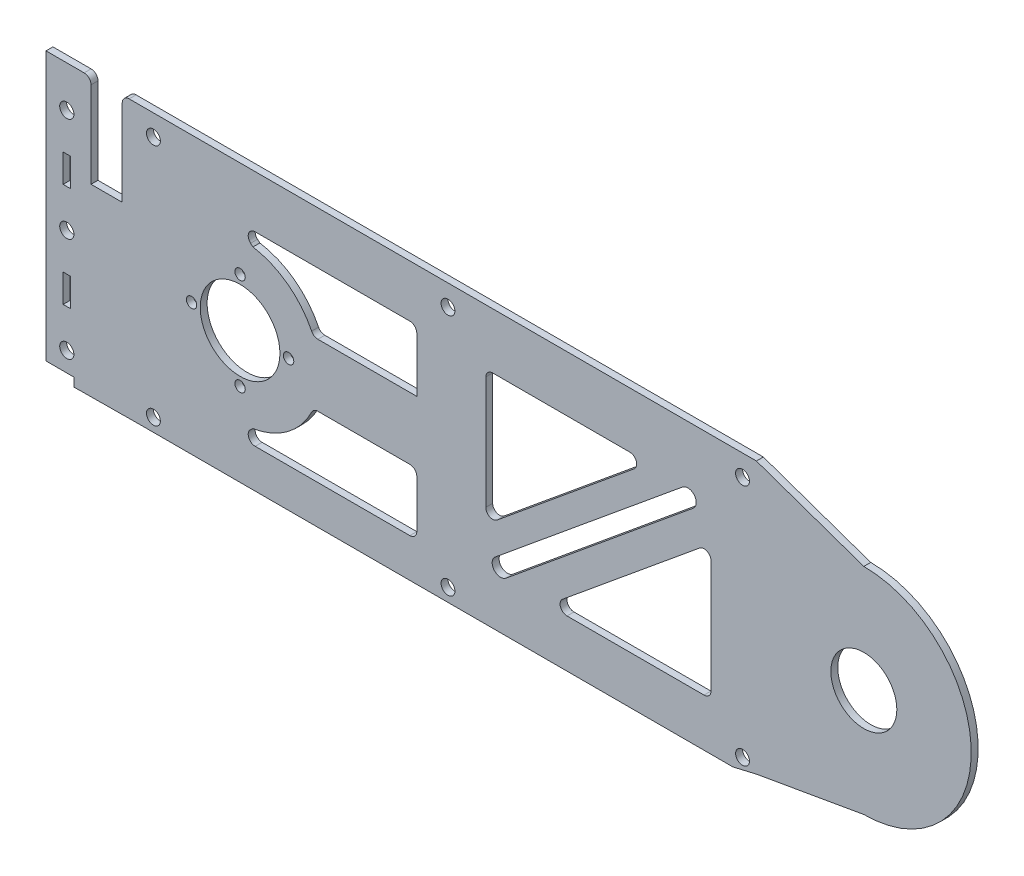
SolidWorks part; units mm, degrees
ref_plane "前视基准面" through (0, 0, 0) normal (0, 0, 1) x (1, 0, 0)
ref_plane "上视基准面" through (0, 0, 0) normal (0, 1, 0) x (1, 0, 0)
ref_plane "右视基准面" through (0, 0, 0) normal (1, 0, 0) x (0, 0, -1)
sketch "草图1" plane through (0, 0, 0) normal (0, 0, 1) x (1, 0, 0)
  line L0 (1.6429, 32.0043) -> (1.6429, 27.9043)
  line L1 (1.6429, 18.9543) -> (1.6429, 10.9543) construction
  line L2 (0.5929, 10.9043) -> (2.6929, 10.9043)
  line L3 (0.5929, 10.9043) -> (0.5929, 19.0043)
  line L4 (0.5929, 19.0043) -> (2.6929, 19.0043)
  line L5 (2.6929, 10.9043) -> (2.6929, 19.0043)
  line L6 (0.5929, 10.9043) -> (2.6929, 19.0043) construction
  line L7 (0.5929, 19.0043) -> (2.6929, 10.9043) construction
  line L12 (1.6429, -0.0457) -> (-4.3571, -0.0457) construction
  line L13 (-4.3571, -0.0457) -> (-4.3571, 41.8043)
  line L14 (-4.3571, 41.8043) -> (262.6429, 41.8043) construction
  line L15 (262.6429, 41.8043) -> (262.6429, -38.1957) construction
  line L18 (51.6429, -0.0457) -> (97.8433, -0.0457) construction
  line L19 (51.6429, -0.0457) -> (231.6429, -0.0457) construction
  line L21 (200.6429, -0.0457) -> (200.6429, 41.8043) construction
  line L23 (200.6429, 41.8043) -> (231.6429, 30.9543)
  line L26 (231.6429, -31.0457) -> (200.6561, -36.4559)
  line L28 (-4.3571, 41.8043) -> (8.6429, 41.8043)
  line L29 (1.6429, -0.0457) -> (37.6429, -0.0457) construction
  line L32 (22.4658, -38.0457) -> (193.8469, -38.0457)
  line L42 (17.6429, 14.9543) -> (17.6429, 41.8043)
  line L43 (17.6429, 41.8043) -> (200.6429, 41.8043)
  line L44 (8.6429, 41.8043) -> (8.6429, 14.9543)
  line L45 (8.6429, 14.9543) -> (17.6429, 14.9543)
  line L47 (193.8469, -38.0457) -> (200.6561, -36.4559)
  line L48 (0.5929, -19.0957) -> (2.6929, -10.9957) construction
  line L49 (0.5929, -10.9957) -> (2.6929, -19.0957) construction
  line L50 (1.6429, -19.0457) -> (1.6429, -11.0457) construction
  line L51 (2.6929, -10.9957) -> (2.6929, -19.0957)
  line L52 (0.5929, -19.0957) -> (2.6929, -19.0957)
  line L53 (0.5929, -10.9957) -> (0.5929, -19.0957)
  line L54 (0.5929, -10.9957) -> (2.6929, -10.9957)
  line L55 (-4.3571, -35.7026) -> (3.7929, -35.7026)
  line L56 (3.7929, -35.7026) -> (3.7929, -38.1957)
  line L57 (3.7929, -38.1957) -> (22.4658, -38.0457)
  line L58 (-4.3571, -35.7026) -> (-4.3571, -0.0457)
  circle A0 centre (1.6429, 29.9543) radius 2.05
  circle A1 centre (1.6429, -0.0457) radius 2.05
  circle A2 centre (1.6429, -30.0457) radius 2.05
  circle A3 centre (51.6429, -0.0457) radius 11.5
  circle A4 centre (51.6429, -0.0457) radius 14 construction
  circle A5 centre (51.6429, -14.0457) radius 1.5
  circle A12 centre (37.6429, -0.0457) radius 1.5
  circle A13 centre (51.6429, 13.9543) radius 1.5
  circle A14 centre (65.6429, -0.0457) radius 1.5
  circle A15 centre (231.6429, -0.0457) radius 9.525
  circle A16 centre (231.6429, -0.0457) radius 31 construction
  arc A17 (231.6429, 30.9543) -> (231.6429, -31.0457) centre (231.6429, -0.0457) cw
  point P6 (1.6429, 14.9543)
  point P56 (1.6429, -15.0457)
  dimension "D3" = 23
  dimension "D4" = 4
  dimension "D13" = 19.05
  dimension "D1" = 8.1
  dimension "D2" = 2.1
  dimension "D5" = 50
  dimension "D7" = 15
  dimension "D8" = 60
  dimension "D9" = 30
  dimension "D11" = 41.85
  dimension "D12" = 31
  dimension "D14" = 180
  dimension "D17" = 13
extrude "凸台-拉伸1" add sketch "草图1" along normal blind 2 contours L58 L15 L14 L13 A2 A1 A0 L5 L2 L3 L4 L54 L53 L52 L51 region at (123.8499, 1.4588, 0)
sketch "草图2" plane through (0, 0, 2) normal (0, 0, 1) x (1, 0, 0)
  line L0 (111.6429, -34.2457) -> (196.6429, 35.7543) construction
  line L1 (196.6429, 35.7543) -> (196.6429, -34.2457) construction
  line L2 (196.6429, -34.2457) -> (111.6429, -34.2457) construction
  line L3 (187.5429, -24.2457) -> (140.4162, -24.2457)
  line L4 (140.4162, -24.2457) -> (187.5429, 14.5645)
  line L5 (187.5429, 14.5645) -> (187.5429, -24.2457)
  line L6 (111.6429, -34.2457) -> (111.6429, 35.7543) construction
  line L7 (111.6429, 35.7543) -> (196.6429, 35.7543) construction
  line L8 (122.5429, 25.7543) -> (169.6695, 25.7543)
  line L9 (122.5429, -13.0559) -> (169.6695, 25.7543)
  line L10 (122.5429, -13.0559) -> (122.5429, 25.7543)
  line L11 (26.6429, 35.7543) -> (51.6429, 13.9543) construction
  line L13 (65.6429, -0.0457) -> (111.6429, -0.0457) construction
  line L18 (17.6429, 41.8043) -> (200.6429, 41.8043) construction
  line L19 (17.6429, 14.9543) -> (17.6429, 41.8043) construction
  line L20 (126.8224, -21.7449) -> (180.8575, 22.7546) construction
  line L23 (26.6429, 35.7543) -> (111.6429, 35.7543) construction
  line L24 (111.6429, -0.0457) -> (111.6429, 35.7543) construction
  line L25 (72.8089, 8.9543) -> (102.6429, 8.9543)
  line L26 (102.6429, 8.9543) -> (102.6429, 26.7543)
  line L27 (50.6579, 26.7543) -> (102.6429, 26.7543)
  line L28 (50.6579, 26.7543) -> (55.3631, 22.6514)
  line L29 (102.6429, -9.0457) -> (102.6429, -26.8457)
  line L30 (72.8089, -9.0457) -> (102.6429, -9.0457)
  line L31 (50.6579, -26.8457) -> (55.3631, -22.7429)
  line L32 (50.6579, -26.8457) -> (102.6429, -26.8457)
  line L38 (125.279, -19.8708) -> (179.3141, 24.6287)
  line L39 (128.3658, -23.619) -> (182.4009, 20.8805)
  circle A0 centre (26.6429, 35.7543) radius 2
  circle A1 centre (111.6429, 35.7543) radius 2
  circle A2 centre (196.6429, 35.7543) radius 2
  circle A3 centre (111.6429, -34.2457) radius 2
  circle A4 centre (196.6429, -34.2457) radius 2
  circle A5 centre (26.6429, -34.2457) radius 2
  arc A8 (51.6429, 13.9543) -> (65.6429, -0.0457) centre (51.6429, -0.0457) cw construction
  arc A9 (55.3631, 22.6514) -> (72.8089, 8.9543) centre (51.6429, -0.0457) cw
  arc A10 (55.3631, -22.7429) -> (72.8089, -9.0457) centre (51.6429, -0.0457) ccw
  arc A11 (125.279, -19.8708) -> (128.3658, -23.619) centre (126.8224, -21.7449) ccw
  arc A12 (182.4009, 20.8805) -> (179.3141, 24.6287) centre (180.8575, 22.7546) ccw
  point P24 (26.6429, 35.8043)
  point P31 (153.84, 0.5049)
  point P42 (0, 0)
  dimension "D3" = 9
  dimension "D4" = 9
  dimension "D1" = 6
  dimension "D2" = 9
  dimension "D5" = 85
  dimension "D6" = 85
  dimension "D7" = 70
extrude "切除-拉伸1" cut sketch "草图2" against normal blind 4
fillet "圆角1" radius 2 15 edges at (187.5429, -24.2457, 1) (140.4162, -24.2457, 1) (187.5429, 14.5645, 1) (169.6695, 25.7543, 1) (122.5429, -13.0559, 1) (122.5429, 25.7543, 1) (72.8089, 8.9543, 1) (72.8089, -9.0457, 1) (50.6579, -26.8457, 1) (102.6429, -26.8457, 1) (50.6579, 26.7543, 1) (102.6429, 26.7543, 1) (102.6429, -9.0457, 1) (17.6429, 41.8043, 1) (8.6429, 41.8043, 1)
